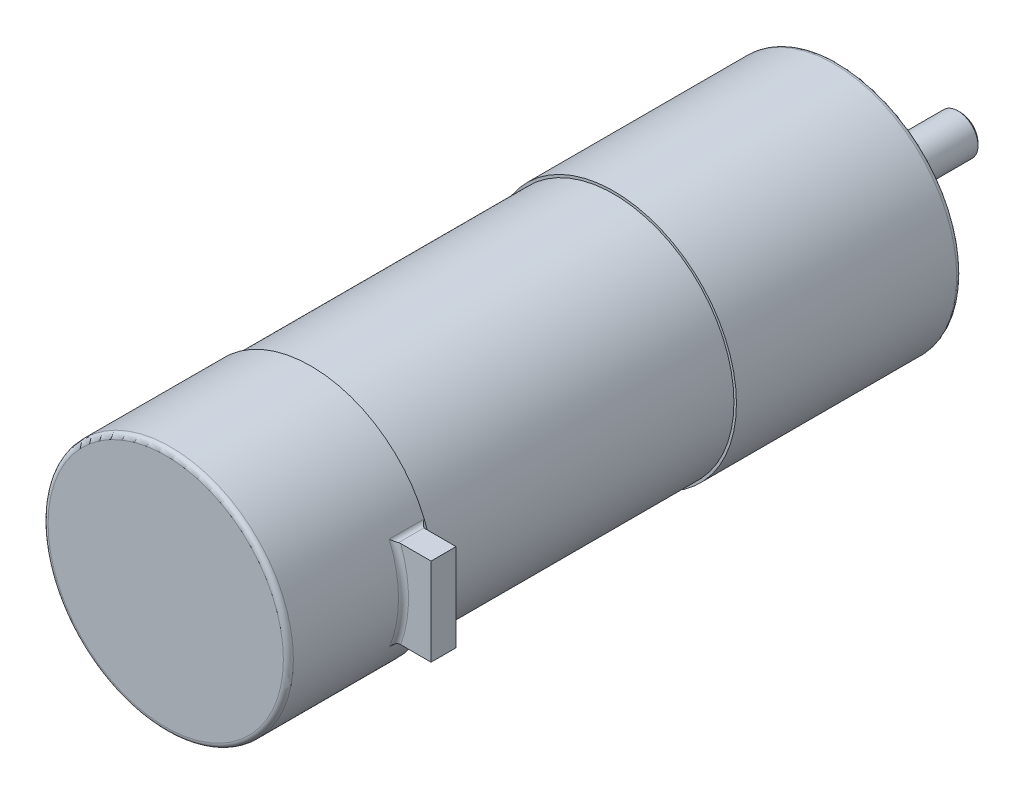
SolidWorks part; units mm, degrees
material "6061-T6 (SS)"
ref_plane "Front Plane" through (0, 0, 0) normal (0, 0, 1) x (1, 0, 0)
ref_plane "Top Plane" through (0, 0, 0) normal (0, 1, 0) x (1, 0, 0)
ref_plane "Right Plane" through (0, 0, 0) normal (1, 0, 0) x (0, 0, -1)
sketch "Sketch1" plane through (0, 0, 0) normal (0, 0, 1) x (1, 0, 0)
  circle A0 centre (0, 0) radius 12.446
  dimension "D1" = 24.892
extrude "Boss-Extrude1" add sketch "Sketch1" along normal blind 22.86
sketch "Sketch2" plane through (0, 0, 22.86) normal (0, 0, 1) x (1, 0, 0)
  circle A0 centre (0, 0) radius 12.192
  dimension "D1" = 24.384
extrude "Boss-Extrude2" add sketch "Sketch2" along normal blind 30.734
sketch "Sketch3" plane through (0, 0, 53.594) normal (0, 0, 1) x (1, 0, 0)
  circle A0 centre (0, 0) radius 12.446
  dimension "D1" = 24.892
extrude "Boss-Extrude3" add sketch "Sketch3" along normal blind 14.732
sketch "Sketch4" plane through (0, 0, 0) normal (0, 0, -1) x (-1, 0, 0)
  circle A0 centre (0, 0) radius 3.5179
  dimension "D1" = 7.0358
extrude "Boss-Extrude4" add sketch "Sketch4" along normal blind 2.794
sketch "Sketch5" plane through (0, 0, 0) normal (0, 0, -1) x (-1, 0, 0)
  circle A0 centre (0, 0) radius 2.032
  dimension "D1" = 4.064
extrude "Boss-Extrude5" add sketch "Sketch5" along normal blind 12.319
chamfer "Chamfer1" distance 0.254 angle 45 1 edges at (-2.032, 0, -12.319)
fillet "Fillet1" radius 0.635 1 edges at (-3.5179, 0, -2.794)
fillet "Fillet2" radius 0.254 1 edges at (-3.5179, 0, 0)
fillet "Fillet3" radius 0.508 2 edges at (12.446, 0, 68.326) (12.446, 0, 0)
sketch "Sketch6" plane through (0, 0, 0) normal (0, 0, -1) x (-1, 0, 0)
  line L0 (0, 0) -> (0, 12.446) construction
  line L1 (-8.6995, 0) -> (0, 0) construction
  circle A0 centre (-8.6995, 0) radius 1.5
  circle A1 centre (0, 0) radius 12.446 construction
  circle A2 centre (8.6995, 0) radius 1.5
  dimension "D1" = 3
  dimension "D2" = 17.399
extrude "Cut-Extrude1" cut sketch "Sketch6" against normal blind 7.62
sketch "Sketch7" plane through (0, 0, 0) normal (1, 0, 0) x (0, -1, 0)
  line L0 (-4.445, -54.102) -> (4.445, -54.102)
  line L1 (4.445, -54.102) -> (4.445, -56.642)
  line L2 (4.445, -56.642) -> (-4.445, -56.642)
  line L3 (-4.445, -56.642) -> (-4.445, -54.102)
  line L4 (0, -68.326) -> (0, 49931.674) construction
  line L5 (-11.938, -68.326) -> (11.938, -68.326) construction
  line L6 (12.446, -53.594) -> (-12.446, -53.594) construction
  point P5 (0, -54.102)
  point P11 (0, -68.326)
  dimension "D1" = 8.89
  dimension "D2" = 2.54
  dimension "D3" = 0.508
extrude "Boss-Extrude6" add sketch "Sketch7" along normal blind 15.24
fillet "Fillet4" radius 0.508 4 edges at (11.6252, -4.445, 55.372) (12.446, 0, 54.102) (11.6252, 4.445, 55.372) (12.446, 0, 56.642)
